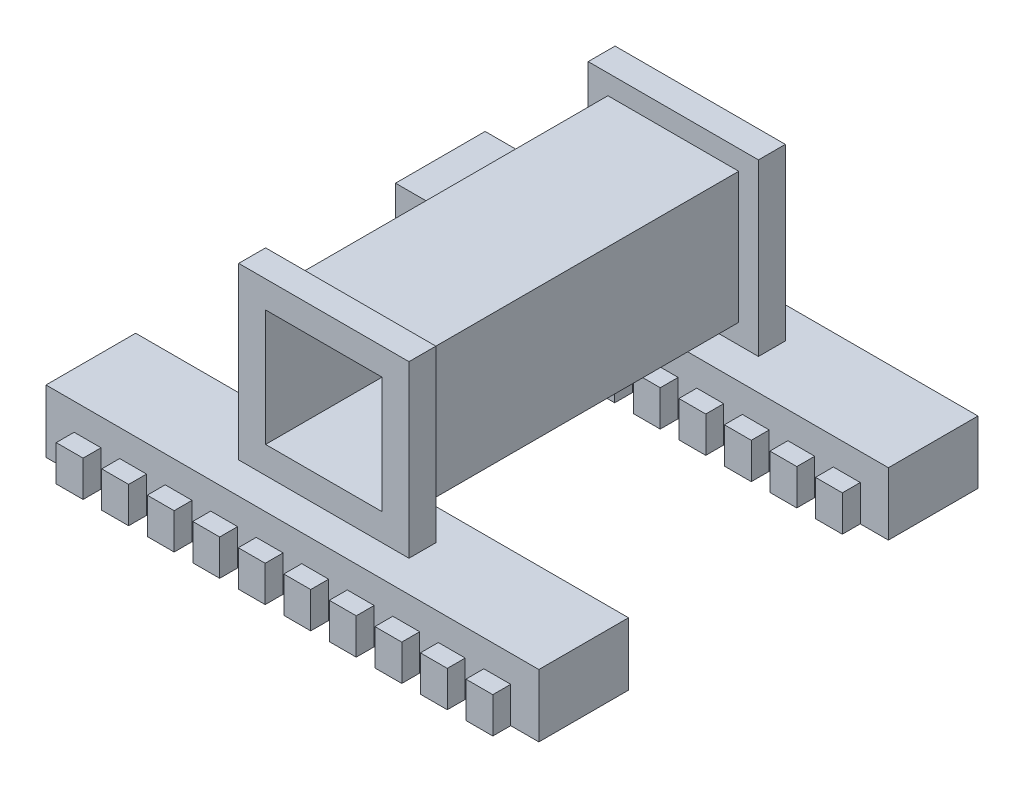
SolidWorks part; units mm, degrees
ref_plane "前视基准面" through (0, 0, 0) normal (0, 0, 1) x (1, 0, 0)
ref_plane "上视基准面" through (0, 0, 0) normal (0, 1, 0) x (1, 0, 0)
ref_plane "右视基准面" through (0, 0, 0) normal (1, 0, 0) x (0, 0, -1)
sketch "草图1" plane through (0, 0, 0) normal (0, 0, 1) x (1, 0, 0)
  line L0 (-9.5, 9.5) -> (9.5, 9.5)
  line L1 (-6.5, -6.5) -> (6.5, -6.5)
  line L2 (-6.5, -6.5) -> (-6.5, 6.5)
  line L3 (-6.5, 6.5) -> (6.5, 6.5)
  line L4 (6.5, -6.5) -> (6.5, 6.5)
  line L5 (-6.5, -6.5) -> (6.5, 6.5) construction
  line L6 (-6.5, 6.5) -> (6.5, -6.5) construction
  line L7 (9.5, -9.5) -> (9.5, 9.5)
  line L8 (-9.5, -9.5) -> (9.5, -9.5)
  line L9 (-9.5, -9.5) -> (-9.5, 9.5)
  line L10 (-7.3, 7.3) -> (7.3, 7.3)
  line L11 (7.3, -7.3) -> (7.3, 7.3)
  line L12 (-7.3, -7.3) -> (7.3, -7.3)
  line L13 (-7.3, -7.3) -> (-7.3, 7.3)
  line L15 (-27.5, -9.5) -> (27.5, -9.5)
  line L16 (-27.5, -9.5) -> (-27.5, -16.5)
  line L17 (-27.5, -16.5) -> (27.5, -16.5)
  line L18 (27.5, -9.5) -> (27.5, -16.5)
  point P0 (0, 0)
  dimension "D1" = 3
  dimension "D2" = 0.8
extrude "凸台-拉伸1" add sketch "草图1" along normal mid plane 42 contours L18 L15 L8 L16 L17 | L9 L8 L7 L0 L12 L13 L10 L11 | L13 L10 L11 L12 region at (0, 9.2313, 0) region at (0, -13, 0)
extrude "切除-拉伸1" cut sketch "草图1<3>" against normal mid plane 42 contours L2 L3 L4 L1
sketch "草图1<3>" plane through (0, 0, 0) normal (0, 0, 1) x (1, 0, 0) same geometry as "草图1"
sketch "草图2" plane through (0, 0, 0) normal (1, 0, 0) x (0, 0, -1)
  line L0 (21, -16.5) -> (21, -9.5) construction
  line L1 (21, -9.5) -> (-21, -9.5) construction
  line L2 (-21, -9.5) -> (-21, -16.5) construction
  line L3 (-21, -16.5) -> (21, -16.5) construction
  line L4 (21, -9.5) -> (21, 9.5) construction
  line L5 (21, 9.5) -> (-21, 9.5) construction
  line L6 (-21, 9.5) -> (-21, -9.5) construction
  line L7 (-21, -9.5) -> (21, -9.5) construction
  line L8 (21, -16.5) -> (21, -9.5)
  line L9 (21, -9.5) -> (-21, -9.5)
  line L10 (-21, -9.5) -> (-21, -16.5)
  line L11 (-21, -16.5) -> (21, -16.5)
  line L12 (21, -9.5) -> (21, 9.5)
  line L13 (21, 9.5) -> (-21, 9.5)
  line L14 (-21, 9.5) -> (-21, -9.5)
  line L15 (-21, -9.5) -> (21, -9.5)
extrude "切除-拉伸6" cut sketch "草图1<12>" against normal mid plane 36 contours L1 L4 L3 L2 | L9 L0 L7 L8 | L13 L10 L11 L12 region at (0, 0, 0)
sketch "草图1<12>" plane through (0, 0, 0) normal (0, 0, 1) x (1, 0, 0) same geometry as "草图1"
extrude "切除-拉伸7" cut sketch "草图1<13>" against normal mid plane 29 contours L18 L15 L8 L16 L17 region at (0, -13, 0)
sketch "草图1<13>" plane through (0, 0, 0) normal (0, 0, 1) x (1, 0, 0) same geometry as "草图1"
sketch "草图4" plane through (0, 0, 0) normal (1, 0, 0) x (0, 0, -1)
  line L0 (-21, -9.5) -> (-14.5, -9.5) construction
  line L1 (-14.5, -9.5) -> (-14.5, -16.5) construction
  line L2 (-14.5, -16.5) -> (-21, -16.5) construction
  line L3 (-21, -16.5) -> (-21, -9.5) construction
  line L4 (-18, 9.5) -> (-18, -9.5) construction
  line L5 (-18, -9.5) -> (-21, -9.5) construction
  line L6 (-21, -9.5) -> (-21, 9.5) construction
  line L7 (-21, 9.5) -> (-18, 9.5) construction
  line L8 (-18, -7.3) -> (-18, 7.3) construction
  line L9 (-18, 7.3) -> (18, 7.3) construction
  line L10 (18, 7.3) -> (18, -7.3) construction
  line L11 (18, -7.3) -> (-18, -7.3) construction
  line L12 (21, -9.5) -> (18, -9.5) construction
  line L13 (18, -9.5) -> (18, 9.5) construction
  line L14 (18, 9.5) -> (21, 9.5) construction
  line L15 (21, 9.5) -> (21, -9.5) construction
  line L16 (14.5, -16.5) -> (14.5, -9.5) construction
  line L17 (14.5, -9.5) -> (21, -9.5) construction
  line L18 (21, -9.5) -> (21, -16.5) construction
  line L19 (21, -16.5) -> (14.5, -16.5) construction
  line L20 (-21, -9.5) -> (-14.5, -9.5)
  line L21 (-14.5, -9.5) -> (-14.5, -16.5)
  line L22 (-14.5, -16.5) -> (-21, -16.5)
  line L23 (-21, -16.5) -> (-21, -9.5)
  line L24 (-18, 9.5) -> (-18, -9.5)
  line L25 (-18, -9.5) -> (-21, -9.5)
  line L26 (-21, -9.5) -> (-21, 9.5)
  line L27 (-21, 9.5) -> (-18, 9.5)
  line L28 (-18, -7.3) -> (-18, 7.3)
  line L29 (-18, 7.3) -> (18, 7.3)
  line L30 (18, 7.3) -> (18, -7.3)
  line L31 (18, -7.3) -> (-18, -7.3)
  line L32 (21, -9.5) -> (18, -9.5)
  line L33 (18, -9.5) -> (18, 9.5)
  line L34 (18, 9.5) -> (21, 9.5)
  line L35 (21, 9.5) -> (21, -9.5)
  line L36 (14.5, -16.5) -> (14.5, -9.5)
  line L37 (14.5, -9.5) -> (21, -9.5)
  line L38 (21, -9.5) -> (21, -16.5)
  line L39 (21, -16.5) -> (14.5, -16.5)
  line L40 (21, -9.5) -> (24.5, -9.5)
  line L41 (24.5, -9.5) -> (24.5, -16.5)
  line L42 (24.5, -16.5) -> (21, -16.5)
  line L43 (-21, -16.5) -> (-24.5049, -16.5)
  line L44 (-24.5049, -16.5) -> (-24.5049, -9.5)
  line L45 (-24.5049, -9.5) -> (-21, -9.5)
extrude "凸台-拉伸2" add sketch "草图4" along normal mid plane 55 contours L42 L41 L40 L38 | L45 L44 L43 L23 region at (0, -13, 22.7525) region at (0, -13, -22.75)
sketch "草图10" plane through (27.5, 0, 0) normal (1, 0, 0) x (0, 0, -1)
  line L0 (-24.5049, -16.5) -> (-25.5049, -16.5)
  line L1 (-24.5049, -16.5) -> (-24.5049, -9.5)
  line L2 (-24.5049, -9.5) -> (-25.5049, -9.5)
  line L3 (-25.5049, -9.5) -> (-25.5049, -16.5)
  line L4 (-14.5, -16.5) -> (-13.5, -16.5)
  line L5 (-13.5, -16.5) -> (-13.5, -9.5)
  line L6 (-13.5, -9.5) -> (-14.5, -9.5)
  line L7 (-14.5, -9.5) -> (-14.5, -16.5)
  line L8 (14.4975, -9.5) -> (14.4975, -16.5)
  line L11 (-0.0012, -16.5) -> (-0.0012, -9.5)
  line L12 (13.4975, -9.5) -> (14.4975, -9.5)
  line L13 (13.4975, -16.5) -> (13.4975, -9.5)
  line L14 (14.4975, -16.5) -> (13.4975, -16.5)
  line L15 (25.5025, -9.5) -> (25.5025, -16.5)
  line L16 (24.5025, -9.5) -> (25.5025, -9.5)
  line L17 (24.5025, -16.5) -> (24.5025, -9.5)
  line L18 (24.5025, -16.5) -> (25.5025, -16.5)
extrude "凸台-拉伸4" add sketch "草图10" against normal blind 55 contours L7 L4 L5 L6 | L3 L0 L1 L2
sketch "草图14" plane through (27.5, 0, 0) normal (1, 0, 0) x (0, 0, -1)
  line L0 (14.5, -9.5) -> (13.5, -9.5)
  line L1 (14.5, -16.5) -> (13.5, -16.5)
  line L2 (13.5, -16.5) -> (13.5, -9.5)
  line L3 (24.5, -9.5) -> (25.5, -9.5)
  line L4 (24.5, -16.5) -> (25.5, -16.5)
  line L5 (25.5, -16.5) -> (25.5, -9.5)
  line L6 (24.5, -9.5) -> (24.5, -16.5)
  line L7 (14.5, -9.5) -> (14.5, -16.5)
extrude "凸台-拉伸6" add sketch "草图14" against normal blind 55
sketch "草图26" plane through (27.5, 0, 0) normal (1, 0, 0) x (0, 0, -1)
  line L0 (25.5, -9.5) -> (26.5, -9.5)
  line L1 (25.5, -16.5) -> (26.5, -16.5)
  line L2 (26.5, -16.5) -> (26.5, -9.5)
  line L3 (25.5, -9.5) -> (25.5, -16.5)
  line L4 (13.5, -9.5) -> (12.5, -9.5)
  line L5 (13.5, -16.5) -> (12.5, -16.5)
  line L6 (12.5, -16.5) -> (12.5, -9.5)
  line L7 (13.5, -9.5) -> (13.5, -16.5)
  line L8 (-13.5, -9.5) -> (-12.5, -9.5)
  line L9 (-12.5, -9.5) -> (-12.5, -16.5)
  line L10 (-12.5, -16.5) -> (-13.5, -16.5)
  line L11 (-13.5, -16.5) -> (-13.5, -9.5)
  line L12 (-25.5049, -9.5) -> (-26.5049, -9.5)
  line L13 (-25.5049, -16.5) -> (-26.5049, -16.5)
  line L14 (-26.5049, -16.5) -> (-26.5049, -9.5)
  line L15 (-25.5049, -9.5) -> (-25.5049, -16.5)
extrude "凸台-拉伸7" add sketch "草图26" against normal blind 55
sketch "草图27" plane through (0, 0, -26.5) normal (0, 0, -1) x (-1, 0, 0)
  line L1 (27.5, -16.5) -> (-27.5, -16.5) construction
  line L2 (-22.86, -16.5) -> (-22.86, -12.5)
  line L3 (-21.36, -16.5) -> (-24.36, -16.5)
  line L4 (-17.78, -12.5) -> (-17.78, -16.5)
  line L5 (-21.36, -16.5) -> (-21.36, -12.5)
  line L6 (-12.7, -16.5) -> (-12.7, -12.5)
  line L7 (-21.36, -12.5) -> (-24.36, -12.5)
  line L8 (-7.62, -12.5) -> (-7.62, -16.5)
  line L9 (-24.36, -16.5) -> (-24.36, -12.5)
  line L10 (-2.54, -16.5) -> (-2.54, -12.5)
  line L11 (-21.36, -16.5) -> (-24.36, -12.5) construction
  line L12 (2.54, -12.5) -> (2.54, -16.5)
  line L13 (-21.36, -12.5) -> (-24.36, -16.5) construction
  line L14 (7.62, -16.5) -> (7.62, -12.5)
  line L15 (-19.28, -16.5) -> (-16.28, -16.5)
  line L16 (12.7, -12.5) -> (12.7, -16.5)
  line L17 (-19.28, -16.5) -> (-19.28, -12.5)
  line L18 (17.78, -16.5) -> (17.78, -12.5)
  line L19 (-19.28, -12.5) -> (-16.28, -12.5)
  line L20 (22.86, -12.5) -> (22.86, -16.5)
  line L21 (-16.28, -16.5) -> (-16.28, -12.5)
  line L22 (-19.28, -16.5) -> (-16.28, -12.5) construction
  line L23 (-19.28, -12.5) -> (-16.28, -16.5) construction
  line L24 (-14.2, -16.5) -> (-11.2, -16.5)
  line L25 (-14.2, -16.5) -> (-14.2, -12.5)
  line L26 (-14.2, -12.5) -> (-11.2, -12.5)
  line L27 (-11.2, -16.5) -> (-11.2, -12.5)
  line L28 (-14.2, -16.5) -> (-11.2, -12.5) construction
  line L29 (-14.2, -12.5) -> (-11.2, -16.5) construction
  line L30 (-6.12, -16.5) -> (-9.12, -16.5)
  line L31 (-6.12, -16.5) -> (-6.12, -12.5)
  line L32 (-6.12, -12.5) -> (-9.12, -12.5)
  line L33 (-9.12, -16.5) -> (-9.12, -12.5)
  line L34 (-6.12, -16.5) -> (-9.12, -12.5) construction
  line L35 (-6.12, -12.5) -> (-9.12, -16.5) construction
  line L36 (-1.04, -16.5) -> (-4.04, -16.5)
  line L37 (-1.04, -16.5) -> (-1.04, -12.5)
  line L38 (-1.04, -12.5) -> (-4.04, -12.5)
  line L39 (-4.04, -16.5) -> (-4.04, -12.5)
  line L40 (-1.04, -16.5) -> (-4.04, -12.5) construction
  line L41 (-1.04, -12.5) -> (-4.04, -16.5) construction
  line L42 (1.04, -16.5) -> (4.04, -16.5)
  line L43 (1.04, -16.5) -> (1.04, -12.5)
  line L44 (1.04, -12.5) -> (4.04, -12.5)
  line L45 (4.04, -16.5) -> (4.04, -12.5)
  line L46 (1.04, -16.5) -> (4.04, -12.5) construction
  line L47 (1.04, -12.5) -> (4.04, -16.5) construction
  line L48 (9.12, -16.5) -> (6.12, -16.5)
  line L49 (9.12, -16.5) -> (9.12, -12.5)
  line L50 (9.12, -12.5) -> (6.12, -12.5)
  line L51 (6.12, -16.5) -> (6.12, -12.5)
  line L52 (9.12, -16.5) -> (6.12, -12.5) construction
  line L53 (9.12, -12.5) -> (6.12, -16.5) construction
  line L54 (11.2, -16.5) -> (14.2, -16.5)
  line L55 (11.2, -16.5) -> (11.2, -12.5)
  line L56 (11.2, -12.5) -> (14.2, -12.5)
  line L57 (14.2, -16.5) -> (14.2, -12.5)
  line L58 (11.2, -16.5) -> (14.2, -12.5) construction
  line L59 (11.2, -12.5) -> (14.2, -16.5) construction
  line L60 (16.28, -16.5) -> (19.28, -16.5)
  line L61 (16.28, -16.5) -> (16.28, -12.5)
  line L62 (16.28, -12.5) -> (19.28, -12.5)
  line L63 (19.28, -16.5) -> (19.28, -12.5)
  line L64 (16.28, -16.5) -> (19.28, -12.5) construction
  line L65 (16.28, -12.5) -> (19.28, -16.5) construction
  line L66 (24.36, -16.5) -> (21.36, -16.5)
  line L67 (24.36, -16.5) -> (24.36, -12.5)
  line L68 (24.36, -12.5) -> (21.36, -12.5)
  line L69 (21.36, -16.5) -> (21.36, -12.5)
  line L70 (24.36, -16.5) -> (21.36, -12.5) construction
  line L71 (24.36, -12.5) -> (21.36, -16.5) construction
  point P0 (-22.86, -14.5)
  point P28 (-17.78, -14.5)
  point P33 (-12.7, -14.5)
  point P38 (-7.62, -14.5)
  point P43 (-2.54, -14.5)
  point P48 (2.54, -14.5)
  point P53 (7.62, -14.5)
  point P58 (12.7, -14.5)
  point P63 (17.78, -14.5)
  point P68 (22.86, -14.5)
  line M16 (-27.5, -9.5) -> (-27.5, -16.5)
  line M17 (-27.5, -16.5) -> (27.5, -16.5)
  line M18 (27.5, -16.5) -> (27.5, -9.5)
  line M19 (27.5, -9.5) -> (-27.5, -9.5)
extrude "切除-拉伸27" cut sketch "草图27" against normal blind 2 contours L69 L68 L67 L9 L7 L5 L17 L19 L21 L25 L26 L27 L33 L32 L31 L39 L38 L37 L43 L44 L45 L51 L50 L49 L55 L56 L57 L61 M17 M18 M19 M16 region at (0, -12.3208, -26.5)
sketch "草图28" plane through (0, 0, 12.5) normal (0, 0, -1) x (-1, 0, 0)
  line L0 (21.36, -16.5) -> (24.36, -16.5) construction
  line L1 (24.36, -16.5) -> (24.36, -12.5) construction
  line L2 (24.36, -12.5) -> (21.36, -12.5) construction
  line L3 (21.36, -12.5) -> (21.36, -16.5) construction
  line L4 (-27.5, -9.5) -> (-27.5, -16.5)
  line L5 (-27.5, -16.5) -> (27.5, -16.5)
  line L6 (27.5, -16.5) -> (27.5, -9.5)
  line L7 (27.5, -9.5) -> (-27.5, -9.5)
  line L8 (-27.5, -9.5) -> (-27.5, -16.5)
  line L9 (-27.5, -16.5) -> (27.5, -16.5)
  line L10 (27.5, -16.5) -> (27.5, -9.5)
  line L11 (27.5, -9.5) -> (-27.5, -9.5)
  line L12 (16.28, -16.5) -> (19.28, -16.5) construction
  line L13 (19.28, -16.5) -> (19.28, -12.5) construction
  line L14 (19.28, -12.5) -> (16.28, -12.5) construction
  line L15 (16.28, -12.5) -> (16.28, -16.5) construction
  line L16 (11.2, -16.5) -> (14.2, -16.5) construction
  line L17 (14.2, -16.5) -> (14.2, -12.5) construction
  line L18 (14.2, -12.5) -> (11.2, -12.5) construction
  line L19 (11.2, -12.5) -> (11.2, -16.5) construction
  line L20 (6.12, -16.5) -> (9.12, -16.5) construction
  line L21 (9.12, -16.5) -> (9.12, -12.5) construction
  line L22 (9.12, -12.5) -> (6.12, -12.5) construction
  line L23 (6.12, -12.5) -> (6.12, -16.5) construction
  line L24 (1.04, -16.5) -> (4.04, -16.5) construction
  line L25 (4.04, -16.5) -> (4.04, -12.5) construction
  line L26 (4.04, -12.5) -> (1.04, -12.5) construction
  line L27 (1.04, -12.5) -> (1.04, -16.5) construction
  line L28 (-4.04, -16.5) -> (-1.04, -16.5) construction
  line L29 (-1.04, -16.5) -> (-1.04, -12.5) construction
  line L30 (-1.04, -12.5) -> (-4.04, -12.5) construction
  line L31 (-4.04, -12.5) -> (-4.04, -16.5) construction
  line L32 (-9.12, -16.5) -> (-6.12, -16.5) construction
  line L33 (-6.12, -16.5) -> (-6.12, -12.5) construction
  line L34 (-6.12, -12.5) -> (-9.12, -12.5) construction
  line L35 (-9.12, -12.5) -> (-9.12, -16.5) construction
  line L36 (-14.2, -16.5) -> (-11.2, -16.5) construction
  line L37 (-11.2, -16.5) -> (-11.2, -12.5) construction
  line L38 (-11.2, -12.5) -> (-14.2, -12.5) construction
  line L39 (-14.2, -12.5) -> (-14.2, -16.5) construction
  line L40 (-19.28, -16.5) -> (-16.28, -16.5) construction
  line L41 (-16.28, -16.5) -> (-16.28, -12.5) construction
  line L42 (-16.28, -12.5) -> (-19.28, -12.5) construction
  line L43 (-19.28, -12.5) -> (-19.28, -16.5) construction
  line L44 (-24.36, -16.5) -> (-21.36, -16.5) construction
  line L45 (-21.36, -16.5) -> (-21.36, -12.5) construction
  line L46 (-21.36, -12.5) -> (-24.36, -12.5) construction
  line L47 (-24.36, -12.5) -> (-24.36, -16.5) construction
  line L48 (21.36, -16.5) -> (24.36, -16.5)
  line L49 (24.36, -16.5) -> (24.36, -12.5)
  line L50 (24.36, -12.5) -> (21.36, -12.5)
  line L51 (21.36, -12.5) -> (21.36, -16.5)
  line L52 (16.28, -16.5) -> (19.28, -16.5)
  line L53 (19.28, -16.5) -> (19.28, -12.5)
  line L54 (19.28, -12.5) -> (16.28, -12.5)
  line L55 (16.28, -12.5) -> (16.28, -16.5)
  line L56 (11.2, -16.5) -> (14.2, -16.5)
  line L57 (14.2, -16.5) -> (14.2, -12.5)
  line L58 (14.2, -12.5) -> (11.2, -12.5)
  line L59 (11.2, -12.5) -> (11.2, -16.5)
  line L60 (6.12, -16.5) -> (9.12, -16.5)
  line L61 (9.12, -16.5) -> (9.12, -12.5)
  line L62 (9.12, -12.5) -> (6.12, -12.5)
  line L63 (6.12, -12.5) -> (6.12, -16.5)
  line L64 (1.04, -16.5) -> (4.04, -16.5)
  line L65 (4.04, -16.5) -> (4.04, -12.5)
  line L66 (4.04, -12.5) -> (1.04, -12.5)
  line L67 (1.04, -12.5) -> (1.04, -16.5)
  line L68 (-4.04, -16.5) -> (-1.04, -16.5)
  line L69 (-1.04, -16.5) -> (-1.04, -12.5)
  line L70 (-1.04, -12.5) -> (-4.04, -12.5)
  line L71 (-4.04, -12.5) -> (-4.04, -16.5)
  line L72 (-9.12, -16.5) -> (-6.12, -16.5)
  line L73 (-6.12, -16.5) -> (-6.12, -12.5)
  line L74 (-6.12, -12.5) -> (-9.12, -12.5)
  line L75 (-9.12, -12.5) -> (-9.12, -16.5)
  line L76 (-14.2, -16.5) -> (-11.2, -16.5)
  line L77 (-11.2, -16.5) -> (-11.2, -12.5)
  line L78 (-11.2, -12.5) -> (-14.2, -12.5)
  line L79 (-14.2, -12.5) -> (-14.2, -16.5)
  line L80 (-19.28, -16.5) -> (-16.28, -16.5)
  line L81 (-16.28, -16.5) -> (-16.28, -12.5)
  line L82 (-16.28, -12.5) -> (-19.28, -12.5)
  line L83 (-19.28, -12.5) -> (-19.28, -16.5)
  line L84 (-24.36, -16.5) -> (-21.36, -16.5)
  line L85 (-21.36, -16.5) -> (-21.36, -12.5)
  line L86 (-21.36, -12.5) -> (-24.36, -12.5)
  line L87 (-24.36, -12.5) -> (-24.36, -16.5)
  line M5 (-27.5, -9.5) -> (-27.5, -16.5)
  line M6 (-27.5, -16.5) -> (27.5, -16.5)
  line M7 (27.5, -16.5) -> (27.5, -9.5)
  line M8 (27.5, -9.5) -> (-27.5, -9.5)
  dimension "D1" = 0
extrude "切除-拉伸28" cut sketch "草图28" against normal blind 2 contours L87 L86 L85 L83 L82 L81 L79 L78 L77 L75 L74 L73 L71 L70 L69 L67 L66 L65 L63 L62 L61 L59 L58 L57 L55 L54 L53 L51 L50 L49 M6 M7 M8 M5 region at (0, -12.3208, 12.5)
sketch "草图29" plane through (0, 0, -12.5) normal (0, 0, 1) x (1, 0, 0)
  line L0 (14.2, -16.5) -> (11.2, -16.5) construction
  line L1 (11.2, -16.5) -> (11.2, -12.5) construction
  line L2 (11.2, -12.5) -> (14.2, -12.5) construction
  line L3 (14.2, -12.5) -> (14.2, -16.5) construction
  line L4 (27.5, -16.5) -> (27.5, -9.5)
  line L5 (27.5, -9.5) -> (-27.5, -9.5)
  line L6 (-27.5, -9.5) -> (-27.5, -16.5)
  line L7 (-27.5, -16.5) -> (27.5, -16.5)
  line L8 (27.5, -16.5) -> (27.5, -9.5)
  line L9 (27.5, -9.5) -> (-27.5, -9.5)
  line L10 (-27.5, -9.5) -> (-27.5, -16.5)
  line L11 (-27.5, -16.5) -> (27.5, -16.5)
  line L12 (19.28, -16.5) -> (16.28, -16.5) construction
  line L13 (16.28, -16.5) -> (16.28, -12.5) construction
  line L14 (16.28, -12.5) -> (19.28, -12.5) construction
  line L15 (19.28, -12.5) -> (19.28, -16.5) construction
  line L16 (24.36, -16.5) -> (21.36, -16.5) construction
  line L17 (21.36, -16.5) -> (21.36, -12.5) construction
  line L18 (21.36, -12.5) -> (24.36, -12.5) construction
  line L19 (24.36, -12.5) -> (24.36, -16.5) construction
  line L20 (9.12, -16.5) -> (6.12, -16.5) construction
  line L21 (6.12, -16.5) -> (6.12, -12.5) construction
  line L22 (6.12, -12.5) -> (9.12, -12.5) construction
  line L23 (9.12, -12.5) -> (9.12, -16.5) construction
  line L24 (4.04, -16.5) -> (1.04, -16.5) construction
  line L25 (1.04, -16.5) -> (1.04, -12.5) construction
  line L26 (1.04, -12.5) -> (4.04, -12.5) construction
  line L27 (4.04, -12.5) -> (4.04, -16.5) construction
  line L28 (-1.04, -16.5) -> (-4.04, -16.5) construction
  line L29 (-4.04, -16.5) -> (-4.04, -12.5) construction
  line L30 (-4.04, -12.5) -> (-1.04, -12.5) construction
  line L31 (-1.04, -12.5) -> (-1.04, -16.5) construction
  line L32 (-6.12, -16.5) -> (-9.12, -16.5) construction
  line L33 (-9.12, -16.5) -> (-9.12, -12.5) construction
  line L34 (-9.12, -12.5) -> (-6.12, -12.5) construction
  line L35 (-6.12, -12.5) -> (-6.12, -16.5) construction
  line L36 (-11.2, -16.5) -> (-14.2, -16.5) construction
  line L37 (-14.2, -16.5) -> (-14.2, -12.5) construction
  line L38 (-14.2, -12.5) -> (-11.2, -12.5) construction
  line L39 (-11.2, -12.5) -> (-11.2, -16.5) construction
  line L40 (-16.28, -16.5) -> (-19.28, -16.5) construction
  line L41 (-19.28, -16.5) -> (-19.28, -12.5) construction
  line L42 (-19.28, -12.5) -> (-16.28, -12.5) construction
  line L43 (-16.28, -12.5) -> (-16.28, -16.5) construction
  line L44 (-21.36, -16.5) -> (-24.36, -16.5) construction
  line L45 (-24.36, -16.5) -> (-24.36, -12.5) construction
  line L46 (-24.36, -12.5) -> (-21.36, -12.5) construction
  line L47 (-21.36, -12.5) -> (-21.36, -16.5) construction
  line L48 (14.2, -16.5) -> (11.2, -16.5)
  line L49 (11.2, -16.5) -> (11.2, -12.5)
  line L50 (11.2, -12.5) -> (14.2, -12.5)
  line L51 (14.2, -12.5) -> (14.2, -16.5)
  line L52 (19.28, -16.5) -> (16.28, -16.5)
  line L53 (16.28, -16.5) -> (16.28, -12.5)
  line L54 (16.28, -12.5) -> (19.28, -12.5)
  line L55 (19.28, -12.5) -> (19.28, -16.5)
  line L56 (24.36, -16.5) -> (21.36, -16.5)
  line L57 (21.36, -16.5) -> (21.36, -12.5)
  line L58 (21.36, -12.5) -> (24.36, -12.5)
  line L59 (24.36, -12.5) -> (24.36, -16.5)
  line L60 (9.12, -16.5) -> (6.12, -16.5)
  line L61 (6.12, -16.5) -> (6.12, -12.5)
  line L62 (6.12, -12.5) -> (9.12, -12.5)
  line L63 (9.12, -12.5) -> (9.12, -16.5)
  line L64 (4.04, -16.5) -> (1.04, -16.5)
  line L65 (1.04, -16.5) -> (1.04, -12.5)
  line L66 (1.04, -12.5) -> (4.04, -12.5)
  line L67 (4.04, -12.5) -> (4.04, -16.5)
  line L68 (-1.04, -16.5) -> (-4.04, -16.5)
  line L69 (-4.04, -16.5) -> (-4.04, -12.5)
  line L70 (-4.04, -12.5) -> (-1.04, -12.5)
  line L71 (-1.04, -12.5) -> (-1.04, -16.5)
  line L72 (-6.12, -16.5) -> (-9.12, -16.5)
  line L73 (-9.12, -16.5) -> (-9.12, -12.5)
  line L74 (-9.12, -12.5) -> (-6.12, -12.5)
  line L75 (-6.12, -12.5) -> (-6.12, -16.5)
  line L76 (-11.2, -16.5) -> (-14.2, -16.5)
  line L77 (-14.2, -16.5) -> (-14.2, -12.5)
  line L78 (-14.2, -12.5) -> (-11.2, -12.5)
  line L79 (-11.2, -12.5) -> (-11.2, -16.5)
  line L80 (-16.28, -16.5) -> (-19.28, -16.5)
  line L81 (-19.28, -16.5) -> (-19.28, -12.5)
  line L82 (-19.28, -12.5) -> (-16.28, -12.5)
  line L83 (-16.28, -12.5) -> (-16.28, -16.5)
  line L84 (-21.36, -16.5) -> (-24.36, -16.5)
  line L85 (-24.36, -16.5) -> (-24.36, -12.5)
  line L86 (-24.36, -12.5) -> (-21.36, -12.5)
  line L87 (-21.36, -12.5) -> (-21.36, -16.5)
  line M5 (27.5, -16.5) -> (27.5, -9.5)
  line M6 (27.5, -9.5) -> (-27.5, -9.5)
  line M7 (-27.5, -9.5) -> (-27.5, -16.5)
  line M8 (-27.5, -16.5) -> (27.5, -16.5)
  dimension "D1" = 0
extrude "切除-拉伸29" cut sketch "草图29" against normal blind 2 contours L86 L87 L81 L82 L83 L77 L78 L79 L73 L74 L75 L69 L70 L71 L65 L66 L67 L61 L62 L63 L49 L50 L51 L53 L54 L55 L57 L58 L59 L85 M8 M5 M6 M7 region at (0, -12.3208, -12.5)
sketch "草图30" plane through (0, 0, 26.5049) normal (0, 0, 1) x (1, 0, 0)
  line L0 (-11.2, -16.5) -> (-11.2, -12.5) construction
  line L1 (-11.2, -12.5) -> (-14.2, -12.5) construction
  line L2 (-14.2, -12.5) -> (-14.2, -16.5) construction
  line L3 (-14.2, -16.5) -> (-11.2, -16.5) construction
  line L4 (27.5, -16.5) -> (27.5, -9.5)
  line L5 (27.5, -9.5) -> (-27.5, -9.5)
  line L6 (-27.5, -9.5) -> (-27.5, -16.5)
  line L7 (-27.5, -16.5) -> (27.5, -16.5)
  line L8 (27.5, -16.5) -> (27.5, -9.5)
  line L9 (27.5, -9.5) -> (-27.5, -9.5)
  line L10 (-27.5, -9.5) -> (-27.5, -16.5)
  line L11 (-27.5, -16.5) -> (27.5, -16.5)
  line L12 (-24.36, -12.5) -> (-24.36, -16.5) construction
  line L13 (-24.36, -16.5) -> (-21.36, -16.5) construction
  line L14 (-21.36, -16.5) -> (-21.36, -12.5) construction
  line L15 (-21.36, -12.5) -> (-24.36, -12.5) construction
  line L16 (-16.28, -16.5) -> (-16.28, -12.5) construction
  line L17 (-16.28, -12.5) -> (-19.28, -12.5) construction
  line L18 (-19.28, -12.5) -> (-19.28, -16.5) construction
  line L19 (-19.28, -16.5) -> (-16.28, -16.5) construction
  line L20 (-6.12, -16.5) -> (-6.12, -12.5) construction
  line L21 (-6.12, -12.5) -> (-9.12, -12.5) construction
  line L22 (-9.12, -12.5) -> (-9.12, -16.5) construction
  line L23 (-9.12, -16.5) -> (-6.12, -16.5) construction
  line L24 (-1.04, -16.5) -> (-1.04, -12.5) construction
  line L25 (-1.04, -12.5) -> (-4.04, -12.5) construction
  line L26 (-4.04, -12.5) -> (-4.04, -16.5) construction
  line L27 (-4.04, -16.5) -> (-1.04, -16.5) construction
  line L28 (4.04, -16.5) -> (4.04, -12.5) construction
  line L29 (4.04, -12.5) -> (1.04, -12.5) construction
  line L30 (1.04, -12.5) -> (1.04, -16.5) construction
  line L31 (1.04, -16.5) -> (4.04, -16.5) construction
  line L32 (9.12, -16.5) -> (9.12, -12.5) construction
  line L33 (9.12, -12.5) -> (6.12, -12.5) construction
  line L34 (6.12, -12.5) -> (6.12, -16.5) construction
  line L35 (6.12, -16.5) -> (9.12, -16.5) construction
  line L36 (14.2, -16.5) -> (14.2, -12.5) construction
  line L37 (14.2, -12.5) -> (11.2, -12.5) construction
  line L38 (11.2, -12.5) -> (11.2, -16.5) construction
  line L39 (11.2, -16.5) -> (14.2, -16.5) construction
  line L40 (19.28, -16.5) -> (19.28, -12.5) construction
  line L41 (19.28, -12.5) -> (16.28, -12.5) construction
  line L42 (16.28, -12.5) -> (16.28, -16.5) construction
  line L43 (16.28, -16.5) -> (19.28, -16.5) construction
  line L44 (24.36, -16.5) -> (24.36, -12.5) construction
  line L45 (24.36, -12.5) -> (21.36, -12.5) construction
  line L46 (21.36, -12.5) -> (21.36, -16.5) construction
  line L47 (21.36, -16.5) -> (24.36, -16.5) construction
  line L48 (-11.2, -16.5) -> (-11.2, -12.5)
  line L49 (-11.2, -12.5) -> (-14.2, -12.5)
  line L50 (-14.2, -12.5) -> (-14.2, -16.5)
  line L51 (-14.2, -16.5) -> (-11.2, -16.5)
  line L52 (-24.36, -12.5) -> (-24.36, -16.5)
  line L53 (-24.36, -16.5) -> (-21.36, -16.5)
  line L54 (-21.36, -16.5) -> (-21.36, -12.5)
  line L55 (-21.36, -12.5) -> (-24.36, -12.5)
  line L56 (-16.28, -16.5) -> (-16.28, -12.5)
  line L57 (-16.28, -12.5) -> (-19.28, -12.5)
  line L58 (-19.28, -12.5) -> (-19.28, -16.5)
  line L59 (-19.28, -16.5) -> (-16.28, -16.5)
  line L60 (-6.12, -16.5) -> (-6.12, -12.5)
  line L61 (-6.12, -12.5) -> (-9.12, -12.5)
  line L62 (-9.12, -12.5) -> (-9.12, -16.5)
  line L63 (-9.12, -16.5) -> (-6.12, -16.5)
  line L64 (-1.04, -16.5) -> (-1.04, -12.5)
  line L65 (-1.04, -12.5) -> (-4.04, -12.5)
  line L66 (-4.04, -12.5) -> (-4.04, -16.5)
  line L67 (-4.04, -16.5) -> (-1.04, -16.5)
  line L68 (4.04, -16.5) -> (4.04, -12.5)
  line L69 (4.04, -12.5) -> (1.04, -12.5)
  line L70 (1.04, -12.5) -> (1.04, -16.5)
  line L71 (1.04, -16.5) -> (4.04, -16.5)
  line L72 (9.12, -16.5) -> (9.12, -12.5)
  line L73 (9.12, -12.5) -> (6.12, -12.5)
  line L74 (6.12, -12.5) -> (6.12, -16.5)
  line L75 (6.12, -16.5) -> (9.12, -16.5)
  line L76 (14.2, -16.5) -> (14.2, -12.5)
  line L77 (14.2, -12.5) -> (11.2, -12.5)
  line L78 (11.2, -12.5) -> (11.2, -16.5)
  line L79 (11.2, -16.5) -> (14.2, -16.5)
  line L80 (19.28, -16.5) -> (19.28, -12.5)
  line L81 (19.28, -12.5) -> (16.28, -12.5)
  line L82 (16.28, -12.5) -> (16.28, -16.5)
  line L83 (16.28, -16.5) -> (19.28, -16.5)
  line L84 (24.36, -16.5) -> (24.36, -12.5)
  line L85 (24.36, -12.5) -> (21.36, -12.5)
  line L86 (21.36, -12.5) -> (21.36, -16.5)
  line L87 (21.36, -16.5) -> (24.36, -16.5)
  line M5 (27.5, -16.5) -> (27.5, -9.5)
  line M6 (27.5, -9.5) -> (-27.5, -9.5)
  line M7 (-27.5, -9.5) -> (-27.5, -16.5)
  line M8 (-27.5, -16.5) -> (27.5, -16.5)
  dimension "D1" = 0
extrude "切除-拉伸30" cut sketch "草图30" against normal blind 2 contours L86 L85 L84 L52 L55 L54 L58 L57 L56 L11 L50 L49 L48 L62 L61 L60 L66 L65 L64 L70 L69 L68 L74 L73 L72 L78 L77 L76 L82 L81 L80 M8 M5 M6 M7 region at (0, -12.3208, 26.5049)
sketch "草图31" plane through (0, -16.5, 0) normal (0, -1, 0) x (1, 0, 0)
  line L6 (22.86, 19.5025) -> (24.86, 19.5025)
  line L7 (-22.86, 19.5025) -> (-24.86, 19.5025)
  line L13 (24.86, 23.509) -> (24.86, 20.509)
  line L14 (24.36, 24.5049) -> (27.5, 24.5049) construction
  line L15 (24.86, 24.5049) -> (24.86, 23.509)
  line L16 (24.86, 23.509) -> (-24.86, 23.509)
  line L17 (-24.86, 23.509) -> (-24.86, 20.509)
  line L18 (-24.86, 20.509) -> (24.86, 20.509)
  line L20 (24.86, 15.4959) -> (24.86, 18.4959)
  line L21 (-24.86, 15.4959) -> (-24.86, 18.4959)
  line L22 (-24.86, 18.4959) -> (24.86, 18.4959)
  line L23 (24.86, 15.4959) -> (-24.86, 15.4959)
  line L24 (-24.86, -23.509) -> (-24.86, -20.509)
  line L25 (-24.86, -15.4959) -> (-24.86, -18.4959)
  line L26 (24.86, -15.4959) -> (24.86, -18.4959)
  line L27 (24.86, -23.509) -> (24.86, -20.509)
  line L28 (24.86, -23.509) -> (-24.86, -23.509)
  line L29 (-24.86, -20.509) -> (24.86, -20.509)
  line L30 (-24.86, -18.4959) -> (24.86, -18.4959)
  line L31 (24.86, -15.4959) -> (-24.86, -15.4959)
  dimension "D1" = 2
  dimension "D2" = 3
  dimension "D3" = 49.72
extrude "切除-拉伸31" cut sketch "草图31" against normal blind 4 contours L17 L18 L13 L16 | L23 L20 L22 L21 | L26 L31 L25 L30 | L29 L24 L28 L27 region at (0, -16.5, 22.009) region at (0, -16.5, 16.9959) region at (0, -16.5, -22.009) region at (0, -16.5, -16.9959)
